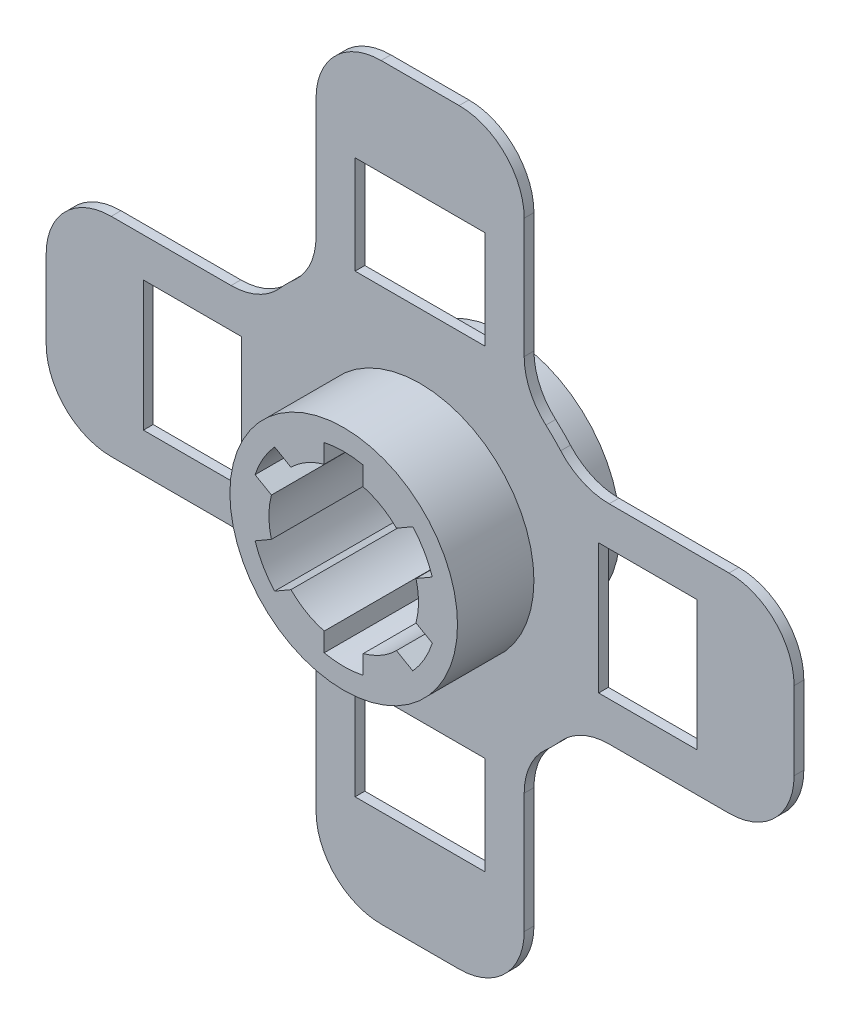
SolidWorks part; units mm, degrees
material "Plain Carbon Steel"
ref_plane "Front Plane" through (0, 0, 0) normal (0, 0, 1) x (1, 0, 0)
ref_plane "Top Plane" through (0, 0, 0) normal (0, 1, 0) x (1, 0, 0)
ref_plane "Right Plane" through (0, 0, 0) normal (1, 0, 0) x (0, 0, -1)
sketch "Sketch1" plane through (0, 0, 0) normal (0, 0, 1) x (1, 0, 0)
  line L0 (0, 87.6808) -> (0, -87.6808) construction
  line L1 (-64.5305, 0) -> (64.5305, 0) construction
  line L2 (-10, 27.45) -> (10, 27.45)
  line L3 (-10, 27.45) -> (-10, 42.55)
  line L4 (-10, 42.55) -> (10, 42.55)
  line L5 (10, 27.45) -> (10, 42.55)
  line L6 (-10, 27.45) -> (10, 42.55) construction
  line L7 (-10, 42.55) -> (10, 27.45) construction
  line L8 (-10, -42.55) -> (10, -42.55)
  line L9 (-10, -42.55) -> (-10, -27.45)
  line L10 (-10, -27.45) -> (10, -27.45)
  line L11 (10, -42.55) -> (10, -27.45)
  line L12 (-10, -42.55) -> (10, -27.45) construction
  line L13 (-10, -27.45) -> (10, -42.55) construction
  line L15 (27.45, -10) -> (42.55, -10)
  line L16 (27.45, -10) -> (27.45, 10)
  line L17 (27.45, 10) -> (42.55, 10)
  line L18 (42.55, -10) -> (42.55, 10)
  line L19 (27.45, -10) -> (42.55, 10) construction
  line L20 (27.45, 10) -> (42.55, -10) construction
  line L21 (-42.55, -10) -> (-27.45, -10)
  line L22 (-42.55, -10) -> (-42.55, 10)
  line L23 (-42.55, 10) -> (-27.45, 10)
  line L24 (-27.45, -10) -> (-27.45, 10)
  line L25 (-42.55, -10) -> (-27.45, 10) construction
  line L26 (-42.55, 10) -> (-27.45, -10) construction
  line L27 (-6, -57.5) -> (6, -57.5)
  line L28 (-16, -47.5) -> (-16, -29.0689)
  line L29 (-6, 57.5) -> (6, 57.5)
  line L30 (16, -47.5) -> (16, -29.0689)
  line L31 (-16, -57.5) -> (16, 57.5) construction
  line L32 (-16, 57.5) -> (16, -57.5) construction
  line L33 (-47.5, -16) -> (-29.0689, -16)
  line L34 (-57.5, -6) -> (-57.5, 6)
  line L35 (-47.5, 16) -> (-29.0689, 16)
  line L36 (57.5, -6) -> (57.5, 6)
  line L37 (-57.5, -16) -> (57.5, 16) construction
  line L38 (-57.5, 16) -> (57.5, -16) construction
  line L41 (29.0689, -16) -> (47.5, -16)
  line L42 (29.0689, 16) -> (47.5, 16)
  line L43 (16, 29.0689) -> (16, 47.5)
  line L44 (-16, 29.0689) -> (-16, 47.5)
  line L46 (-3, 11.1018) -> (-3, 14)
  line L48 (3, 14) -> (3, 11.1018)
  line L49 (8.1144, 8.149) -> (10.6244, 9.5981)
  line L51 (13.6244, 4.4019) -> (11.1144, 2.9528)
  line L52 (11.1144, -2.9528) -> (13.6244, -4.4019)
  line L54 (10.6244, -9.5981) -> (8.1144, -8.149)
  line L55 (3, -11.1018) -> (3, -14)
  line L57 (-3, -14) -> (-3, -11.1018)
  line L58 (-8.1144, -8.149) -> (-10.6244, -9.5981)
  line L60 (-13.6244, -4.4019) -> (-11.1144, -2.9528)
  line L61 (-11.1144, 2.9528) -> (-13.6244, 4.4019)
  line L63 (-10.6244, 9.5981) -> (-8.1144, 8.149)
  circle A0 centre (0, 0) radius 57.5 construction
  circle A1 centre (0, 0) radius 17.5
  arc A2 (-3, 11.1018) -> (-8.1144, 8.149) centre (0, 0) ccw
  arc A3 (-19.3333, 21.6153) -> (-21.6153, 19.3333) centre (0, 0) ccw
  arc A4 (21.6153, 19.3333) -> (19.3333, 21.6153) centre (0, 0) ccw
  arc A5 (19.3333, -21.6153) -> (21.6153, -19.3333) centre (0, 0) ccw
  arc A6 (-21.6153, -19.3333) -> (-19.3333, -21.6153) centre (0, 0) ccw
  arc A7 (6, 57.5) -> (16, 47.5) centre (6, 47.5) cw
  arc A8 (-16, 47.5) -> (-6, 57.5) centre (-6, 47.5) cw
  arc A9 (-57.5, 6) -> (-47.5, 16) centre (-47.5, 6) cw
  arc A10 (-47.5, -16) -> (-57.5, -6) centre (-47.5, -6) cw
  arc A11 (47.5, 16) -> (57.5, 6) centre (47.5, 6) cw
  arc A12 (57.5, -6) -> (47.5, -16) centre (47.5, -6) cw
  arc A13 (-16, -47.5) -> (-6, -57.5) centre (-6, -47.5) ccw
  arc A14 (16, -47.5) -> (6, -57.5) centre (6, -47.5) cw
  arc A15 (-21.6153, -19.3333) -> (-29.0689, -16) centre (-29.0689, -26) ccw
  arc A16 (-16, -29.0689) -> (-19.3333, -21.6153) centre (-26, -29.0689) ccw
  arc A17 (19.3333, -21.6153) -> (16, -29.0689) centre (26, -29.0689) ccw
  arc A18 (29.0689, -16) -> (21.6153, -19.3333) centre (29.0689, -26) ccw
  arc A19 (29.0689, 16) -> (21.6153, 19.3333) centre (29.0689, 26) cw
  arc A20 (16, 29.0689) -> (19.3333, 21.6153) centre (26, 29.0689) ccw
  arc A21 (-19.3333, 21.6153) -> (-16, 29.0689) centre (-26, 29.0689) ccw
  arc A22 (-21.6153, 19.3333) -> (-29.0689, 16) centre (-29.0689, 26) cw
  arc A25 (-8.1144, -8.149) -> (-3, -11.1018) centre (0, 0) ccw
  arc A27 (-11.0791, 3.0829) -> (-11.0791, -3.0829) centre (0, 0) ccw
  arc A28 (3, -11.1018) -> (8.1144, -8.149) centre (0, 0) ccw
  arc A30 (11.0791, -3.0829) -> (11.0791, 3.0829) centre (0, 0) ccw
  arc A32 (8.1144, 8.149) -> (3, 11.1018) centre (0, 0) ccw
  arc A36 (3, 14) -> (-3, 14) centre (0, 0) ccw
  arc A37 (-10.6244, 9.5981) -> (-13.6244, 4.4019) centre (0, 0) ccw
  arc A38 (-13.6244, -4.4019) -> (-10.6244, -9.5981) centre (0, 0) ccw
  arc A39 (-3, -14) -> (3, -14) centre (0, 0) ccw
  arc A40 (10.6244, -9.5981) -> (13.6244, -4.4019) centre (0, 0) ccw
  arc A41 (13.6244, 4.4019) -> (10.6244, 9.5981) centre (0, 0) ccw
  point P6 (0, 35)
  point P9 (0, 0)
  point P14 (0, -35)
  point P19 (35, 0)
  point P22 (0, 0)
  point P27 (-35, 0)
  point P40 (0, 57.5)
  point P41 (-57.5, 0)
  point P81 (24.1868, -16)
  point P86 (16, 24.1868)
  point P89 (-16, 24.1868)
  point P120 (0, 0)
  dimension "D1" = 115
  dimension "D2" = 23
  dimension "D3" = 35
  dimension "D4" = 58
  dimension "D13" = 10
  dimension "D14" = 10
  dimension "D5" = 20
  dimension "D6" = 15.1
  dimension "D7" = 35
  dimension "D8" = 35
  dimension "D9" = 35
  dimension "D10" = 35
  dimension "D11" = 32
  dimension "D12" = 32
  dimension "D16" = 6
  dimension "D17" = 3
  dimension "D18" = 6
extrude "Boss-Extrude1" add sketch "Sketch1" along normal mid plane 1.5 contours A3 A22 L35 A9 L34 A10 L33 A15 A6 A16 L28 A13 L27 A14 L30 A17 A5 A18 L41 A12 L36 A11 L42 A19 A4 A20 L43 A7 L29 A8 L44 A21 L5 L2 L3 L4 L11 L8 L9 L10 L18 L15 L16 L17 L24 L21 L22 region at (-11.9211, -53.4211, 0)
extrude "Boss-Extrude2" add sketch "Sketch1<3>" along normal mid plane 25 contours A1 A2 region at (-17.005, 0, 0)
sketch "Sketch1<3>" plane through (0, 0, 0) normal (0, 0, 1) x (1, 0, 0) same geometry as "Sketch1"
equation "\"a\"= 115"
equation "\"b\"= 35"
equation "\"c\"= 35"
equation "\"d\"= 25"
equation "\"e\"= 1.5"
equation "\"x\"= 1"
equation "\"y\"= 1"
equation "\"z\"= 1"
equation "\"D1@Sketch1\"=\"a\""
equation "\"D3@Sketch1\"=\"b\""
equation "\"D7@Sketch1\"=\"c\""
equation "\"D8@Sketch1\"=\"c\""
equation "\"D9@Sketch1\"=\"c\""
equation "\"D10@Sketch1\"=\"c\""
equation "\"D1@Boss-Extrude1\"=\"e\""
equation "\"D1@Boss-Extrude2\"=\"d\""
